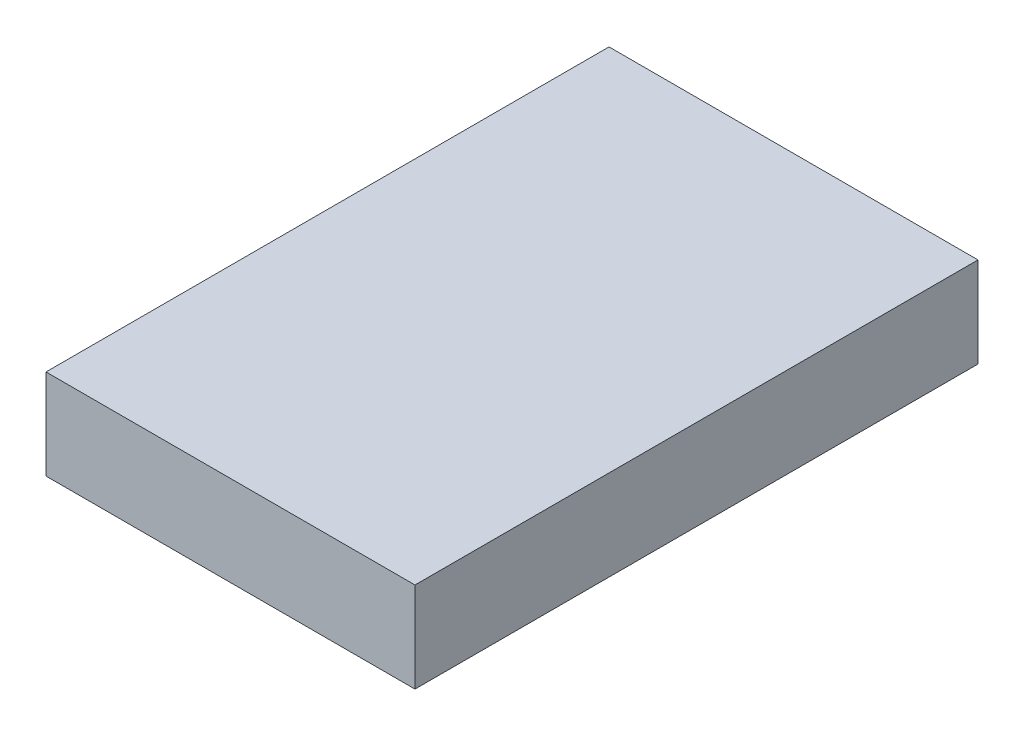
SolidWorks part; units mm, degrees
ref_plane "Front Plane" through (0, 0, 0) normal (0, 0, 1) x (1, 0, 0)
ref_plane "Top Plane" through (0, 0, 0) normal (0, 1, 0) x (1, 0, 0)
ref_plane "Right Plane" through (0, 0, 0) normal (1, 0, 0) x (0, 0, -1)
sketch "Sketch1" plane through (0, 0, 0) normal (0, 1, 0) x (1, 0, 0)
  line L0 (0, 0) -> (135, 206) construction
  line L1 (0, 0) -> (135, 0)
  line L2 (0, 0) -> (0, 206)
  line L3 (0, 206) -> (135, 206)
  line L4 (135, 0) -> (135, 206)
  point P5 (67.5, 103)
extrude "Boss-Extrude1" add sketch "Sketch1" along normal blind 33
ref_axis "Axis1" through (67.5, 0, -103) along (0, -1, 0)
